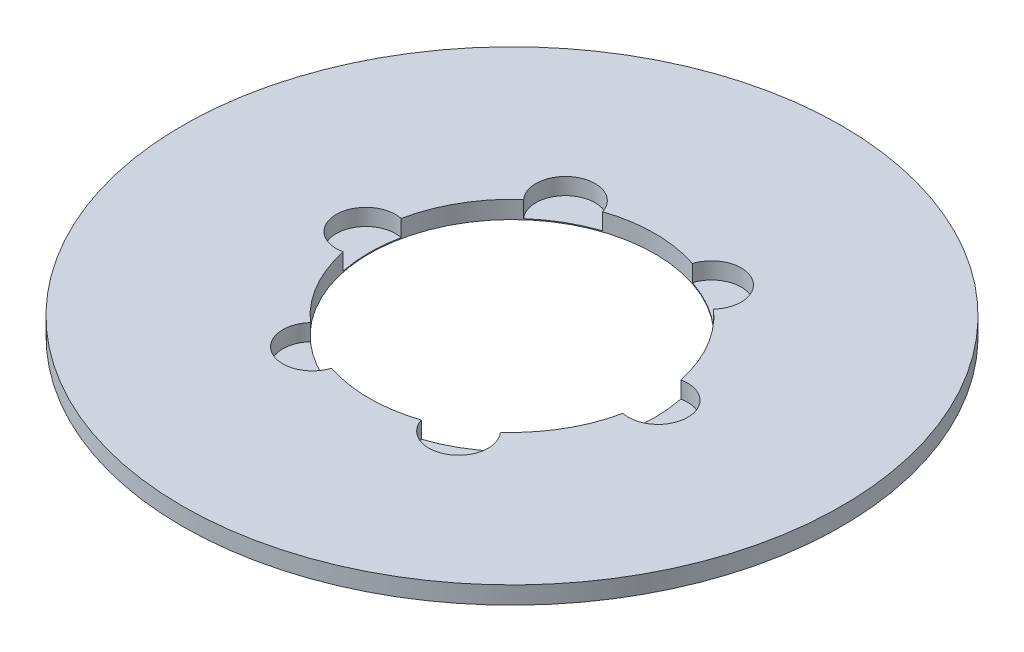
SolidWorks part; units mm, degrees
ref_plane "Front Plane" through (0, 0, 0) normal (0, 0, 1) x (1, 0, 0)
ref_plane "Top Plane" through (0, 0, 0) normal (0, 1, 0) x (1, 0, 0)
ref_plane "Right Plane" through (0, 0, 0) normal (1, 0, 0) x (0, 0, -1)
sketch "Sketch1" plane through (0, 0, 0) normal (0, 1, 0) x (1, 0, 0)
  circle A0 centre (0, 0) radius 75
  dimension "FLANGE_OD" = 150
extrude "Boss-Extrude1" add sketch "Sketch1" along normal blind 4
sketch "Sketch2" plane through (0, 0, 0) normal (0, 1, 0) x (1, 0, 0)
  circle A0 centre (0, 0) radius 32.5
  dimension "BORE_D" = 65
extrude "Cut-Extrude1" cut sketch "Sketch2" along normal through all
sketch "Sketch3" plane through (0, 4, 0) normal (0, 1, 0) x (1, 0, 0)
  circle A0 centre (0, 0) radius 33.2522 construction
  circle A1 centre (-33.2522, 0) radius 6.7428
  dimension "BOLT_D" = 13.4857
  dimension "BOLT_PCD" = 66.5045
extrude "Cut-Extrude2" cut sketch "Sketch3" against normal blind 3.784
pattern_circular "CirPattern1" count 6 over 360 about axis through (0, 0, 0) along (0, 1, 0) of "Cut-Extrude2"
